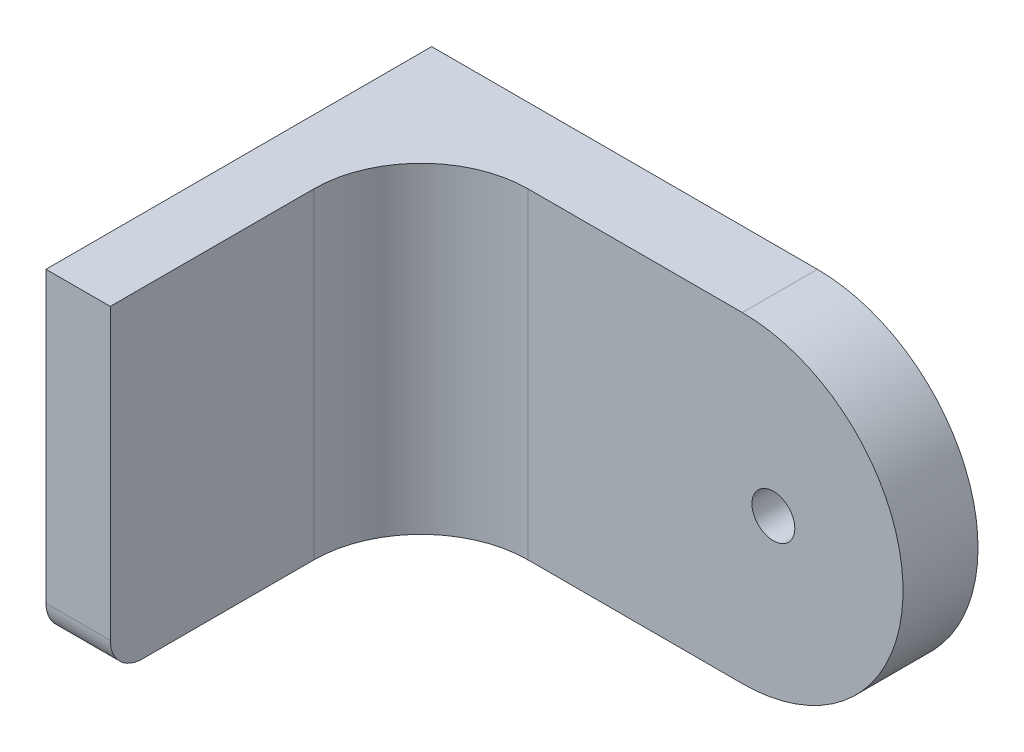
SolidWorks part; units mm, degrees
ref_plane "Front Plane" through (0, 0, 0) normal (0, 0, 1) x (1, 0, 0)
ref_plane "Top Plane" through (0, 0, 0) normal (0, 1, 0) x (1, 0, 0)
ref_plane "Right Plane" through (0, 0, 0) normal (1, 0, 0) x (0, 0, -1)
sketch "Sketch1" plane through (-52.7871, 0, 0.0004) normal (1, 0, 0) x (0, 0, -1)
  line L0 (33.0006, 215.1803) -> (3.0006, 215.18)
  line L3 (3.0006, 215.18) -> (3.0003, 245.18)
  line L4 (3.0003, 245.18) -> (0.0003, 245.18)
  line L5 (0.0003, 245.18) -> (0.0005, 218.18)
  line L8 (0.0003, 245.18) -> (0.0005, 218.18)
  line L9 (33.0003, 245.1803) -> (33.0006, 215.1803)
  line L10 (36.0005, 218.1803) -> (36.0003, 245.1803)
  line L11 (36.0003, 245.1803) -> (33.0003, 245.1803)
  line L13 (36.0005, 218.1803) -> (36.0003, 245.1803)
  line L14 (36.0003, 245.1803) -> (0.0003, 245.18)
  arc A1 (0.0005, 218.18) -> (3.0006, 215.18) centre (3.0005, 218.18) ccw
  arc A2 (0.0005, 218.18) -> (3.0006, 215.18) centre (3.0005, 218.18) ccw
  arc A3 (33.0006, 215.1803) -> (36.0005, 218.1803) centre (33.0005, 218.1803) ccw
  arc A4 (33.0006, 215.1803) -> (36.0005, 218.1803) centre (33.0005, 218.1803) ccw
  dimension "D1" = 0
  dimension "D2" = 0
extrude "Boss-Extrude1" add sketch "Sketch1" along normal blind 6
sketch "Sketch2" plane through (-46.7871, 0, 0.0004) normal (1, 0, 0) x (0, 0, -1)
  line L0 (29.0003, 245.1803) -> (29.0006, 215.1802)
  line L4 (3.0006, 215.18) -> (33.0006, 215.1803)
  line L5 (36.0005, 218.1803) -> (36.0003, 245.1803)
  line L6 (36.0003, 245.1803) -> (0.0003, 245.18)
  line L7 (0.0003, 245.18) -> (0.0005, 218.18)
  line L8 (29.0006, 215.1802) -> (33.0006, 215.1803)
  line L9 (36.0005, 218.1803) -> (36.0003, 245.1803)
  line L10 (36.0003, 245.1803) -> (29.0003, 245.1803)
  arc A2 (0.0005, 218.18) -> (3.0006, 215.18) centre (3.0005, 218.18) ccw
  arc A3 (33.0006, 215.1803) -> (36.0005, 218.1803) centre (33.0005, 218.1803) ccw
  arc A5 (33.0006, 215.1803) -> (36.0005, 218.1803) centre (33.0005, 218.1803) ccw
  dimension "D2" = 7
  dimension "D1" = 0
extrude "Boss-Extrude2" add sketch "Sketch2" along normal blind 45
sketch "Sketch3" plane through (-0.0003, 0.0003, -36.0024) normal (0, 0, -1) x (-1, 0, 0)
  line L0 (2.5959, 215.18) -> (2.5959, 245.18) construction
  line L1 (1.7871, 215.18) -> (52.7871, 215.18) construction
  line L2 (1.7871, 245.18) -> (52.7871, 245.18) construction
  line L3 (2.5959, 230.18) -> (52.7871, 230.18) construction
  line L4 (52.7871, 218.18) -> (52.7871, 245.18) construction
  line L5 (1.7871, 218.18) -> (1.7871, 245.18) construction
  line L6 (16.7871, 215.18) -> (-2.3545, 215.18)
  line L7 (-2.3545, 215.18) -> (-2.3545, 245.18)
  line L8 (-2.3545, 245.18) -> (16.7871, 245.18)
  arc A0 (16.7871, 245.18) -> (16.7871, 215.18) centre (16.7871, 230.18) ccw
extrude "Cut-Extrude1" cut sketch "Sketch3" against normal up to surface (7 mm away) up to face at (-24.2873, 230.1803, -29.0002)
sketch "Sketch4" plane through (-0.0003, 0.0003, -36.0024) normal (0, 0, -1) x (-1, 0, 0)
  line L0 (13.8885, 230.18) -> (13.8885, 247.0307) construction
  line L2 (1.7871, 230.18) -> (13.8885, 230.18) construction
  arc A0 (16.7871, 245.18) -> (7.7871, 218.18) centre (16.7871, 230.18) ccw construction
  circle A1 centre (13.8885, 230.18) radius 2
extrude "Cut-Extrude2" cut sketch "Sketch4" against normal through all
fillet "Fillet1" radius 10 1 edges at (-46.7873, 230.1803, -29)
